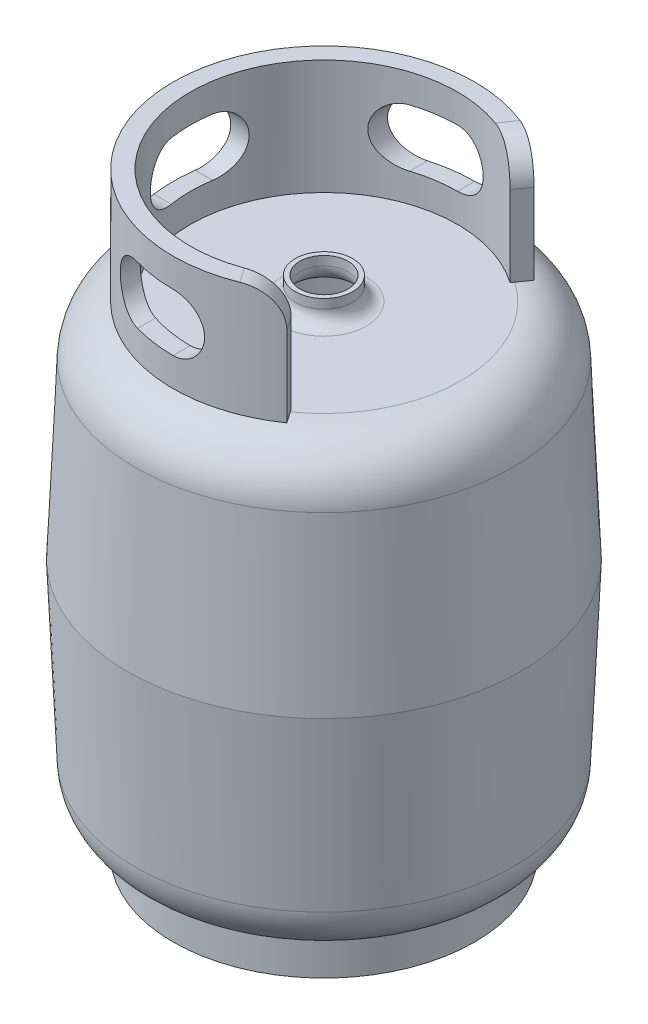
SolidWorks part; units mm, degrees
material "1060 Alloy"
ref_plane "Front Plane" through (0, 0, 0) normal (0, 0, 1) x (1, 0, 0)
ref_plane "Top Plane" through (0, 0, 0) normal (0, 1, 0) x (1, 0, 0)
ref_plane "Right Plane" through (0, 0, 0) normal (1, 0, 0) x (0, 0, -1)
sketch "Sketch1" plane through (0, 0, 0) normal (0, 0, 1) x (1, 0, 0)
  line L0 (0, 338.6029) -> (0, -338.6029) construction
  line L1 (-560.2941, 0) -> (560.2941, 0) construction
  line L2 (0, 213.75) -> (-25, 213.75)
  line L3 (-25, 213.75) -> (-25, 205.75)
  line L4 (-37, 193.75) -> (-119.4219, 193.75)
  line L5 (-164.379, 150.7129) -> (-170.9593, 0)
  line L6 (-170.9593, 0) -> (-164.379, -150.7129)
  line L7 (-119.4219, -193.75) -> (0, -193.75)
  line L8 (0, 213.75) -> (0, -193.75)
  arc A0 (-119.4219, -193.75) -> (-164.379, -150.7129) centre (-119.4219, -148.75) cw
  arc A1 (-164.379, 150.7129) -> (-119.4219, 193.75) centre (-119.4219, 148.75) cw
  arc A2 (-37, 193.75) -> (-25, 205.75) centre (-37, 205.75) ccw
  point P4 (0, 0)
  point P7 (0, 0)
  point P16 (-162.5, -193.75)
  point P19 (-162.5, 193.75)
  point P22 (-25, 193.75)
  dimension "D8" = 45
  dimension "D9" = 12
  dimension "D1" = 193.75
  dimension "D2" = 387.5
  dimension "D3" = 92.5
  dimension "D4" = 92.5
  dimension "D5" = 20
  dimension "D6" = 162.5
  dimension "D7" = 25
revolve "Revolve2" add sketch "Sketch1" angle 360 about L8
shell "Shell2" thickness 4 removed face at (-25, 213.75, 0)
sketch "Sketch3" plane through (0, 193.75, 0) normal (0, 1, 0) x (1, 0, 0)
  line L0 (0, 131.4219) -> (0, -131.4219) construction
  line L1 (66.7768, 95.3672) -> (75.3805, 107.6545)
  line L2 (66.7768, -95.3672) -> (75.3805, -107.6545)
  arc A0 (75.3805, 107.6545) -> (75.3805, -107.6545) centre (0, 0) ccw
  circle A1 centre (0, 0) radius 119.4219 construction
  arc A2 (66.7768, 95.3672) -> (66.7768, -95.3672) centre (0, 0) ccw
  point P9 (0, 0)
  dimension "D1" = 12
  dimension "D2" = 3
  dimension "D3" = 35
  dimension "D4" = 110
extrude "Boss-Extrude1" add sketch "Sketch3" along normal blind 100
sketch "Sketch4" plane through (0, 0, 0) normal (0, 0, 1) x (1, 0, 0)
  line L0 (-36, 243.75) -> (0, 243.75) construction
  line L1 (-36, 268.75) -> (0, 268.75)
  line L2 (-36, 218.75) -> (0, 218.75)
  line L3 (75.3805, 293.75) -> (-131.4219, 293.75) construction
  line L4 (0, -293.75) -> (0, 293.75) construction
  arc A0 (-36, 268.75) -> (-36, 218.75) centre (-36, 243.75) ccw
  arc A1 (0, 218.75) -> (0, 268.75) centre (0, 243.75) ccw
  point P2 (-18, 243.75)
  point P12 (0, 0)
  point P13 (25, 243.75)
  point P15 (-61, 243.75)
  dimension "D2" = 86
  dimension "D1" = 50
  dimension "D3" = 50
  dimension "D4" = 18
extrude "Cut-Extrude2" cut sketch "Sketch4" against normal through all both and the other way through all
sketch "Sketch6" plane through (0, 0, 0) normal (1, 0, 0) x (0, 0, -1)
  line L0 (0, -293.75) -> (0, 293.75) construction
  line L2 (116.4219, 293.75) -> (-116.4219, 293.75) construction
  line L3 (-18, 243.75) -> (18, 243.75) construction
  line L4 (-18, 268.75) -> (18, 268.75)
  line L5 (-18, 218.75) -> (18, 218.75)
  arc A0 (-18, 268.75) -> (-18, 218.75) centre (-18, 243.75) ccw
  arc A1 (18, 218.75) -> (18, 268.75) centre (18, 243.75) ccw
  point P4 (0, 0)
  point P9 (0, 243.75)
  point P14 (43, 243.75)
  point P15 (-43, 243.75)
  dimension "D1" = 50
  dimension "D2" = 86
  dimension "D3" = 50
extrude "Cut-Extrude3" cut sketch "Sketch6" against normal through all both and the other way through all
sketch "Sketch7" plane through (0, -193.75, 0) normal (0, -1, 0) x (-1, 0, 0)
  circle A0 centre (0, 0) radius 131.4219
  circle A1 centre (0, 0) radius 119.4219 construction
  circle A2 centre (0, 0) radius 116.4219
  dimension "D1" = 12
  dimension "D2" = 3
extrude "Boss-Extrude2" add sketch "Sketch7" along normal blind 30
fillet "Fillet1" radius 30 2 edges at (71.0787, 293.75, 101.5109) (71.0787, 293.75, -101.5109)
